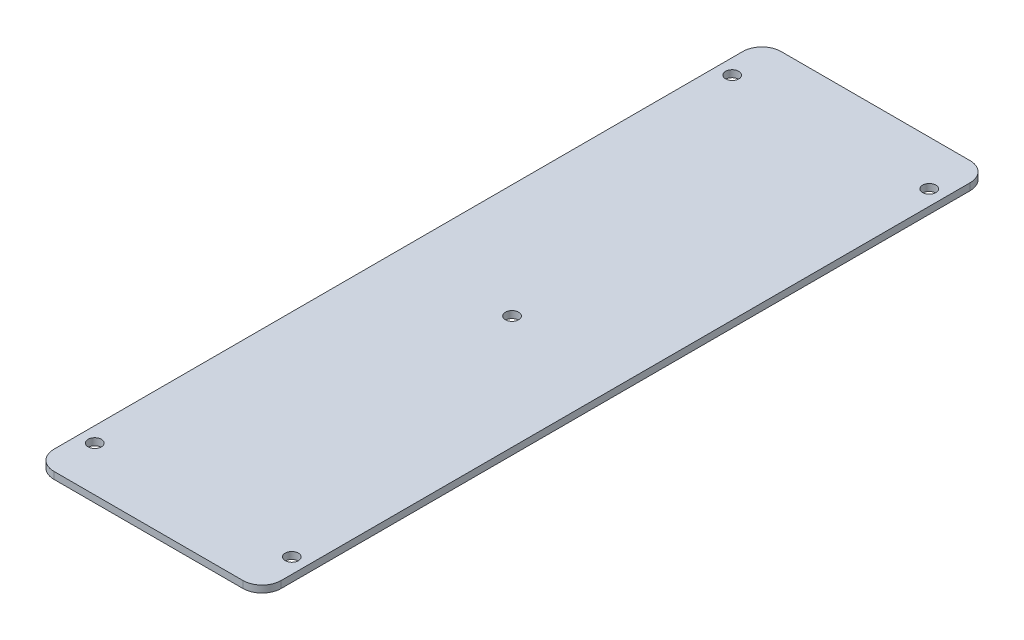
SolidWorks part; units mm, degrees
ref_plane "Front Plane" through (0, 0, 0) normal (0, 0, 1) x (1, 0, 0)
ref_plane "Top Plane" through (0, 0, 0) normal (0, 1, 0) x (1, 0, 0)
ref_plane "Right Plane" through (0, 0, 0) normal (1, 0, 0) x (0, 0, -1)
sketch "Sketch1" plane through (0, 0, 0) normal (0, 1, 0) x (1, 0, 0)
  line L1 (0, 0) -> (49.784, 0)
  line L2 (0, 0) -> (0, -159.258)
  line L3 (0, -159.258) -> (49.784, -159.258)
  line L4 (49.784, 0) -> (49.784, -159.258)
  dimension "D1" = 49.784
  dimension "D2" = 159.258
extrude "Boss-Extrude1" add sketch "Sketch1" along normal blind 1.524
sketch "Sketch2" plane through (0, 1.524, 0) normal (0, 1, 0) x (1, 0, 0)
  line L0 (49.784, 0) -> (0, 0) construction
  line L1 (49.784, -159.258) -> (49.784, 0) construction
  circle A0 centre (46.4693, -9.8298) radius 1.4478
  dimension "D1" = 2.8956
  dimension "D2" = 9.8298
  dimension "D3" = 3.3147
extrude "Cut-Extrude1" cut sketch "Sketch2" against normal up to surface (1.524 mm away) up to face at (24.892, 0, 79.629)
pattern_linear "LPattern1" count 2 spacing 43.1546 along (-1, 0, 0) count 2 spacing 139.5984 along (0, 0, 1) of "Cut-Extrude1"
fillet "Fillet1" radius 4.191 4 edges at (49.784, 0.762, 159.258) (0, 0.762, 159.258) (0, 0.762, 0) (49.784, 0.762, 0)
sketch "Sketch3" plane through (0, 1.524, 0) normal (0, 1, 0) x (1, 0, 0)
  line L0 (24.892, -159.258) -> (24.892, -41.4316) construction
  line L1 (4.191, -159.258) -> (45.593, -159.258) construction
  circle A0 centre (24.892, -79.629) radius 1.4478
  dimension "D1" = 2.8956
  dimension "D2" = 79.629
extrude "Cut-Extrude2" cut sketch "Sketch3" against normal up to surface (1.524 mm away) up to face at (3.3147, 0, 11.2776)
